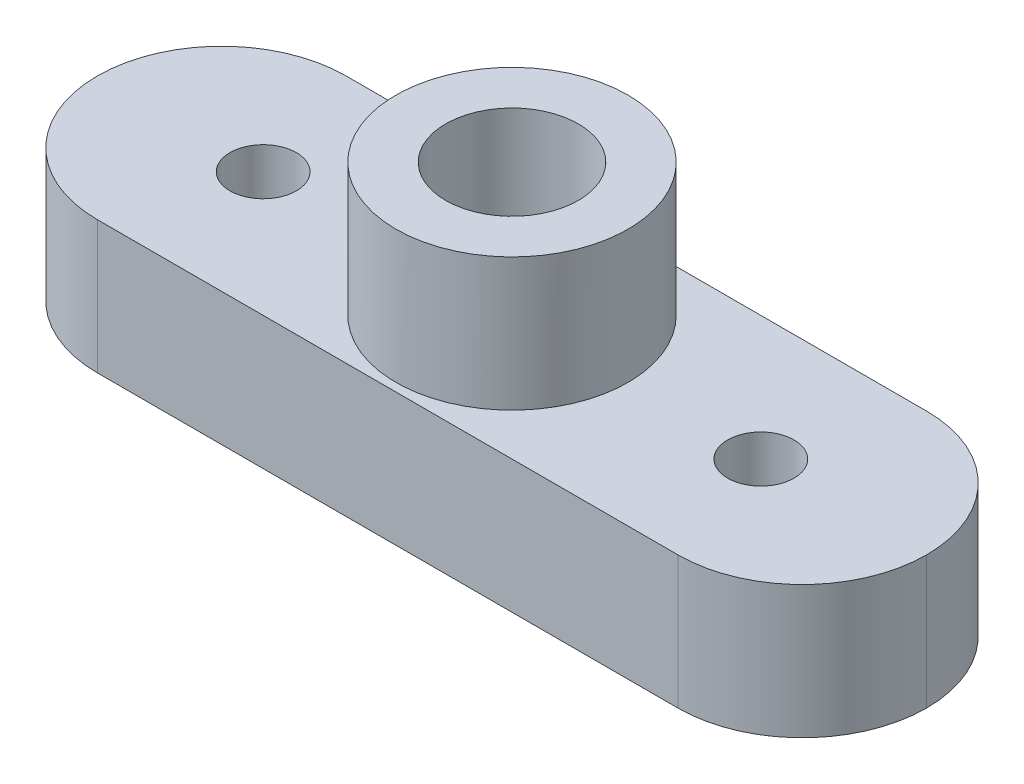
SolidWorks part; units mm, degrees
ref_plane "Plan de face" through (0, 0, 0) normal (0, 0, 1) x (1, 0, 0)
ref_plane "Plan de dessus" through (0, 0, 0) normal (0, 1, 0) x (1, 0, 0)
ref_plane "Plan de droite" through (0, 0, 0) normal (1, 0, 0) x (0, 0, -1)
sketch "Esquisse1" plane through (0, 0, 0) normal (0, 1, 0) x (1, 0, 0)
  line L0 (0, 0) -> (0, -7.5) construction
  line L1 (0, 0) -> (0, 7.5) construction
  line L2 (0, -7.5) -> (25, -7.5)
  line L3 (0, 7.5) -> (25, 7.5)
  line L4 (25, 7.5) -> (25, -7.5)
  line L5 (0, -7.5) -> (-25, -7.5)
  line L6 (-25, -7.5) -> (-25, 7.5)
  line L7 (-25, 7.5) -> (0, 7.5)
  dimension "D1" = 7.5
  dimension "D2" = 7.5
extrude "Boss.-Extru.1" add sketch "Esquisse1" along normal blind 8
fillet "Congé1" radius 7.5 4 edges at (-25, 4, 7.5) (-25, 4, -7.5) (25, 4, -7.5) (25, 4, 7.5)
sketch "Esquisse2" plane through (0, 8, 0) normal (0, 1, 0) x (1, 0, 0)
  line L0 (0, 0) -> (-15, 0) construction
  line L1 (0, 0) -> (15, 0) construction
  circle A0 centre (-15, 0) radius 2
  circle A1 centre (15, 0) radius 2
extrude "Enlèv. mat.-Extru.1" cut sketch "Esquisse2" against normal up to next
sketch "Esquisse3" plane through (0, 8, 0) normal (0, 1, 0) x (1, 0, 0)
  circle A0 centre (0, 0) radius 7
  circle A1 centre (0, 0) radius 4
extrude "Boss.-Extru.2" add sketch "Esquisse3" along normal blind 8
